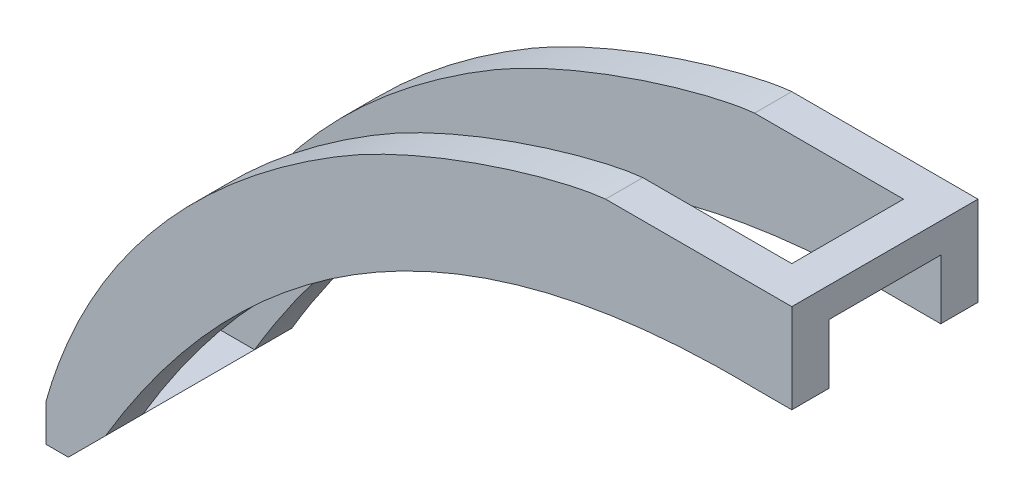
SolidWorks part; units mm, degrees
ref_plane "Ön Düzlem" through (0, 0, 0) normal (0, 0, 1) x (1, 0, 0)
ref_plane "Üst Düzlem" through (0, 0, 0) normal (0, 1, 0) x (1, 0, 0)
ref_plane "Sağ Düzlem" through (0, 0, 0) normal (1, 0, 0) x (0, 0, -1)
sketch "Çizim1" plane through (0, 0, 0) normal (0, 0, 1) x (1, 0, 0)
  line L0 (11.7955, 52.1597) -> (11.7955, 59.1597)
  line L1 (-75.3341, 3.0838) -> (-83.3341, 3.0838)
  line L4 (11.7955, 59.1597) -> (11.7955, 64.1597)
  line L5 (11.7955, 64.1597) -> (-8.2045, 64.1597)
  spline S0 degree 2 poles (11.7955, 52.1597) (-45.4521, 53.3524) (-75.3341, 3.0838) knots 0 0 0 1 1 1
  spline S1 degree 3 poles (-8.2045, 64.1597) (-13.6508, 63.6625) (-29.9336, 59.0693) (-50.9671, 47.5075) (-76.1997, 28.5321) (-83.3341, 3.0838) knots 0.168212 0.168212 0.168212 0.168212 0.597339 0.680517 1 1 1 1
  dimension "D1" = 100
  dimension "D2" = 7
  dimension "D4" = 5
  dimension "D3" = 8
  dimension "D5" = 20
  dimension "D6" = 64.1597
  dimension "D7" = 11.7955
extrude "Yükseklik-Ekstrüzyon1" add sketch "Çizim1" along normal blind 5
sketch "Çizim2" plane through (11.7955, 0, 0) normal (1, 0, 0) x (0, 0, -1)
  line L0 (0, 52.1597) -> (0, 64.1597) construction
  line L1 (-5, 52.1597) -> (20, 52.1597)
  line L2 (-5, 52.1597) -> (-5, 64.1597)
  line L3 (-5, 64.1597) -> (20, 64.1597)
  line L4 (20, 52.1597) -> (20, 64.1597)
  dimension "D1" = 25
extrude "Yükseklik-Ekstrüzyon2" add sketch "Çizim2" along normal blind 5
sketch "Çizim3" plane through (0, 0, -20) normal (0, 0, -1) x (-1, 0, 0)
  line L2 (75.3341, 3.0838) -> (83.3341, 3.0838)
  line L3 (-11.7955, 64.1597) -> (-11.7955, 52.1597)
  line L4 (75.3341, 3.0838) -> (83.3341, 3.0838)
  line L5 (-11.7955, 64.1597) -> (-11.7955, 52.1597)
  line L10 (8.2045, 64.1597) -> (-11.7955, 64.1597)
  line L11 (8.2045, 64.1597) -> (-11.7955, 64.1597)
  parabola Q2 (-11.7955, 52.1597) -> (75.3341, 3.0838) focus (16.6619, 3.6356) apex (36.7889, 41.4844)
  parabola Q4 (-11.7955, 52.1597) -> (75.3341, 3.0838) focus (16.6619, 3.6356) apex (36.7889, 41.4844)
  spline S1 degree 3 poles (-1699.8048, -870.6662) (372.2583, -213.4645) (82.1751, 30.3529) (-25.3376, 89.4512) (-185.8714, 56.84) (1953.8247, -397.3056) knots -1.065934 -1.065934 -1.065934 -1.065934 0.487694 0.570873 3.185748 3.185748 3.185748 3.185748 only from (83.3341, 3.0838) to (8.2045, 64.1597)
  spline S2 degree 3 poles (83.3341, 3.0838) (76.1997, 28.5321) (50.9671, 47.5075) (29.9336, 59.0693) (13.6508, 63.6625) (8.2045, 64.1597) knots 0.168212 0.168212 0.168212 0.168212 0.487694 0.570873 1 1 1 1
  dimension "D1" = 0
extrude "Yükseklik-Ekstrüzyon3" add sketch "Çizim3" against normal blind 5
sketch "Çizim4" plane through (0, 3.0838, 0) normal (0, -1, 0) x (1, 0, 0)
  line L1 (-75.3341, -20) -> (-83.3341, -20)
  line L2 (-75.3341, -20) -> (-75.3341, 5)
  line L3 (-75.3341, 5) -> (-83.3341, 5)
  line L4 (-83.3341, -20) -> (-83.3341, 5)
extrude "Yükseklik-Ekstrüzyon4" add sketch "Çizim4" along normal blind 5
chamfer "Pah1" distance 5 angle 45 1 edges at (-75.3341, -1.9162, -7.5)
sketch "Çizim5" plane through (11.7955, 0, 0) normal (-1, 0, 0) x (0, 0, 1)
  line L0 (-15, 64.1597) -> (0, 64.1597) construction
  line L1 (-15, 64.1597) -> (-15, 52.1597) construction
  line L2 (-15, 48.7333) -> (0, 48.7333)
  line L3 (-15, 48.7333) -> (-15, 60.1597)
  line L4 (-15, 60.1597) -> (0, 60.1597)
  line L5 (0, 52.1597) -> (0, 64.1597) construction
  line L7 (0, 48.7333) -> (0, 60.1597)
  dimension "D1" = 4
extrude "Kes-Ekstrüzyon1" cut sketch "Çizim5" against normal up to next
